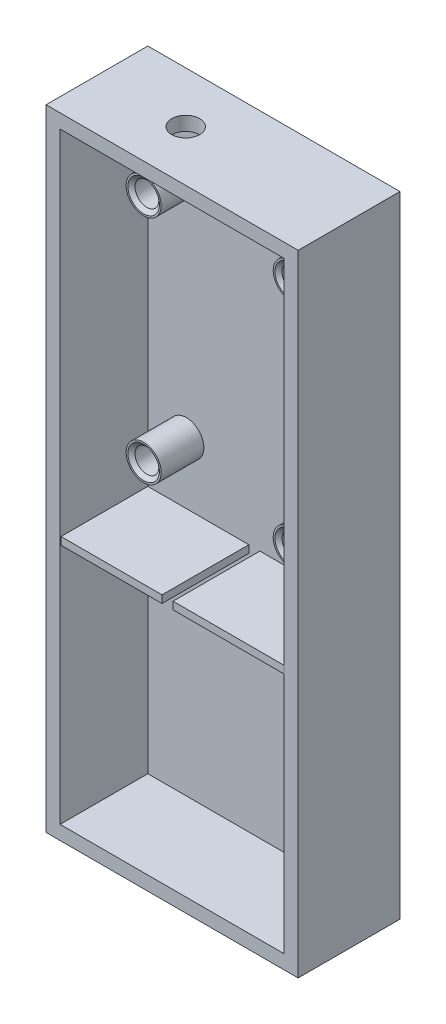
SolidWorks part; units mm, degrees
ref_plane "Front Plane" through (0, 0, 0) normal (0, 0, 1) x (1, 0, 0)
ref_plane "Top Plane" through (0, 0, 0) normal (0, 1, 0) x (1, 0, 0)
ref_plane "Right Plane" through (0, 0, 0) normal (1, 0, 0) x (0, 0, -1)
sketch "Sketch1" plane through (0, 0, 0) normal (0, 0, 1) x (1, 0, 0)
  line L0 (22.86, 57.15) -> (-22.86, -57.15) construction
  line L1 (-22.86, 57.15) -> (22.86, 57.15)
  line L2 (-22.86, 57.15) -> (-22.86, -57.15)
  line L3 (-22.86, -57.15) -> (22.86, -57.15)
  line L4 (22.86, 57.15) -> (22.86, -57.15)
  point P4 (0, 0)
  dimension "D1" = 114.3
  dimension "D2" = 45.72
extrude "Boss-Extrude1" add sketch "Sketch1" along normal mid plane 18.4568 contours L1 L4 L3 L2
shell "Shell3" thickness 2.54 removed face at (0, 0, 9.2284)
sketch "Sketch4" plane through (0, 0, -6.6884) normal (0, 0, 1) x (1, 0, 0)
  line L0 (-13.335, 43.561) -> (13.335, 43.561) construction
  line L1 (-20.32, 54.61) -> (-20.32, -54.61) construction
  line L2 (13.335, 43.561) -> (13.335, 1.651) construction
  line L3 (-20.32, -54.61) -> (20.32, -54.61) construction
  line L4 (13.335, 1.651) -> (-13.335, 1.651) construction
  line L5 (-13.335, 43.561) -> (-13.335, 1.651) construction
  circle A0 centre (-13.335, 43.561) radius 3.175
  circle A2 centre (13.335, 43.561) radius 3.175
  circle A3 centre (13.335, 1.651) radius 3.175
  circle A4 centre (-13.335, 1.651) radius 3.175
  dimension "D1" = 6.35
  dimension "D2" = 26.67
  dimension "D4" = 41.91
  dimension "D6" = 56.261
  dimension "D7" = 56.261
  dimension "D8" = 6.35
  dimension "D9" = 6.35
  dimension "D10" = 6.35
  dimension "D3" = 6.985
  dimension "D5" = 41.91
extrude "Boss-Extrude2" add sketch "Sketch4" along normal blind 7.7458
sketch "Sketch7" plane through (0, 0, 1.0575) normal (0, 0, 1) x (1, 0, 0)
  point P0 (-13.335, 43.561)
  point P1 (13.335, 43.561)
  point P3 (13.335, 1.651)
  point P5 (-13.335, 1.651)
hole_wizard "#8 (0.199) Diameter Hole1" positions "Sketch12" profile "Sketch13" hole size "#8" standard "ANSI Inch" end condition up to next
sketch "Sketch12" plane through (0, 57.15, 0) normal (0, 1, 0) x (1, 0, 0)
  point P0 (-6.7619, 0)
  point P2 (-42.2856, -5.5596)
sketch "Sketch13" plane through (-6.7619, 57.15, 0) normal (1, 0, 0) x (0, 0, 1)
  line L0 (0, 0) -> (0, 2.54)
  line L1 (0, 2.54) -> (2.5273, 2.54)
  line L2 (2.5273, 2.54) -> (2.5273, 0)
  line L5 (2.5273, 0) -> (0, 0)
  line L11 (0, -6.35) -> (0, 107.95) construction
  dimension "Thru Hole Dia." = 5.0546
  dimension "Thru Hole Depth" = 2.54
sketch "Sketch14" plane through (0, 57.15, 0) normal (0, 1, 0) x (1, 0, 0)
  line L1 (3.874, 3.2905) -> (9.8938, 3.2905)
  line L2 (3.874, 3.2905) -> (3.874, -2.7293)
  line L3 (3.874, -2.7293) -> (9.8938, -2.7293)
  line L4 (9.8938, 3.2905) -> (9.8938, -2.7293)
  dimension "D1" = 6.0198
  dimension "D2" = 6.0198
sketch "Sketch19" plane through (0, 0, -6.6884) normal (0, 0, 1) x (1, 0, 0)
  line L0 (-20.32, 54.61) -> (-20.32, -54.61) construction
  line L1 (-20.32, -9.4814) -> (20.32, -9.4814)
  line L2 (-20.32, -9.4814) -> (-20.32, -10.8425)
  line L3 (-20.32, -10.8425) -> (20.32, -10.8425)
  line L4 (20.32, -9.4814) -> (20.32, -10.8425)
  line L5 (20.32, 54.61) -> (20.32, -54.61) construction
extrude "Boss-Extrude3" add sketch "Sketch19" along normal blind 15.748
sketch "Sketch23" plane through (0, -10.8425, 0) normal (0, -1, 0) x (1, 0, 0)
  line L0 (-20.32, 9.0596) -> (20.32, 9.0596) construction
  line L1 (-2.0022, 9.0596) -> (0, 9.0596)
  line L2 (-2.0022, 9.0596) -> (-2.0022, -6.6884)
  line L3 (-2.0022, -6.6884) -> (0, -6.6884)
  line L4 (0, 9.0596) -> (0, -6.6884)
  line L5 (-20.32, -6.6884) -> (20.32, -6.6884) construction
extrude "Cut-Extrude2" cut sketch "Sketch23" against normal blind 15.748
hole_wizard "#4 (0.209) Diameter Hole1" positions "Sketch25" profile "Sketch26" hole size "#4" standard "ANSI Inch"
sketch "Sketch25" plane through (0, 0, 1.0575) normal (0, 0, 1) x (1, 0, 0)
  point P0 (-13.335, 1.651)
  point P3 (-13.335, 43.561)
  point P6 (13.335, 1.651)
  point P9 (13.335, 43.561)
sketch "Sketch26" plane through (-13.335, 1.651, 1.0575) normal (1, 0, 0) x (0, -1, 0)
  line L0 (0, 0) -> (0, 6.8853)
  line L1 (0, 6.8853) -> (2.159, 5.588)
  line L2 (2.159, 5.588) -> (2.159, 0.5861)
  line L3 (2.159, 0.5861) -> (2.8575, 0)
  line L5 (2.8575, 0) -> (0, 0)
  line L6 (-2.159, 0.5861) -> (-2.8575, 0) construction
  line L10 (0, 6.8853) -> (-2.159, 5.588) construction
  line L11 (0, -6.35) -> (0, 107.95) construction
  dimension "Hole Dia." = 4.318
  dimension "Hole Depth" = 5.588
  dimension "Near C'Sink Dia." = 5.715
  dimension "Near C'Sink Angle" = 100
  dimension "Drill Angle" = 118
